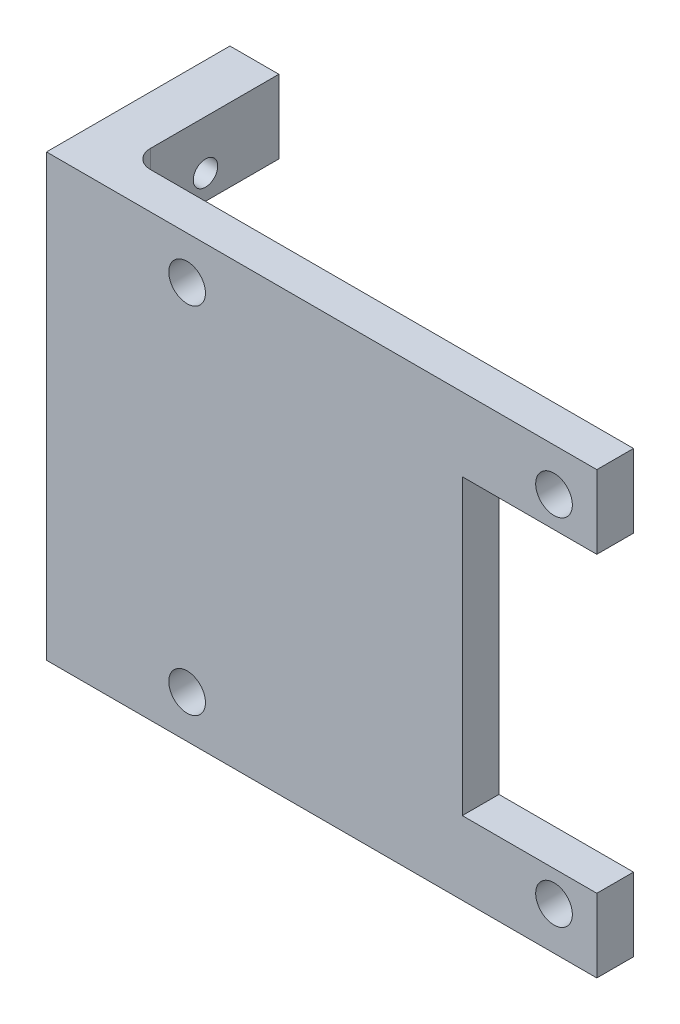
SolidWorks part; units mm, degrees
ref_plane "Front Plane" through (0, 0, 0) normal (0, 0, 1) x (1, 0, 0)
ref_plane "Top Plane" through (0, 0, 0) normal (0, 1, 0) x (1, 0, 0)
ref_plane "Right Plane" through (0, 0, 0) normal (1, 0, 0) x (0, 0, -1)
sketch "Sketch1" plane through (0, 0, 0) normal (0, 0, 1) x (1, 0, 0)
  line L1 (-18.5, 18) -> (18.5, 18)
  line L2 (-18.5, 18) -> (-18.5, -18)
  line L3 (-18.5, -18) -> (18.5, -18)
  line L4 (18.5, 18) -> (18.5, 12)
  line L8 (18.5, 12) -> (7.5, 12)
  line L9 (7.5, 12) -> (7.5, -12)
  line L10 (7.5, -12) -> (18.5, -12)
  line L11 (18.5, -12) -> (18.5, -18)
  point P0 (0, 0)
  dimension "D1" = 36
  dimension "D2" = 37
  dimension "D3" = 18.5
  dimension "D4" = 18
  dimension "D5" = 24
  dimension "D6" = 12
  dimension "D7" = 11
extrude "Boss-Extrude1" add sketch "Sketch1" along normal blind 3
sketch "Sketch2" plane through (0, 0, 0) normal (0, 0, 1) x (1, 0, 0)
  line L0 (-18.5, -18) -> (18.5, -18) construction
  line L1 (-18.5, 18) -> (-18.5, -18) construction
  line L4 (0, -8.25) -> (0, 8.25) construction
  line L5 (8.25, 0) -> (-8.25, 0) construction
  circle A0 centre (-15, -14.5) radius 1.5
  circle A4 centre (15, -14.5) radius 1.5
  circle A5 centre (15, 14.5) radius 1.5
  circle A6 centre (-15, 14.5) radius 1.5
  dimension "D1" = 3
  dimension "D2" = 3.5
  dimension "D3" = 3.5
extrude "Cut-Extrude1" cut sketch "Sketch2" along normal up to next
ref_plane "Plane2" through (-18.5, 0, 0) normal (-1, 0, 0) x (0, 0, 1)
sketch "Sketch6" plane through (-18.5, 0, 0) normal (-1, 0, 0) x (0, 0, 1)
  line L4 (0, 18) -> (0, -18)
  line L5 (0, -18) -> (3, -18)
  line L6 (3, -18) -> (3, 18)
  line L7 (3, 18) -> (0, 18)
  line L8 (0, 18) -> (0, -18)
  line L9 (0, -18) -> (3, -18)
  line L10 (3, -18) -> (3, 18)
  line L11 (3, 18) -> (0, 18)
  dimension "D1" = 0
extrude "Boss-Extrude3" add sketch "Sketch6" along normal blind 8
sketch "Sketch9" plane through (0, 0, 0) normal (0, 0, 1) x (1, 0, 0)
  line L0 (-22.5, 18) -> (-22.5, 12)
  line L1 (18.5, 18) -> (-26.5, 18) construction
  line L2 (-22.5, 12) -> (-26.5, 12)
  line L3 (-26.5, 18) -> (-26.5, -18) construction
  line L4 (-26.5, 12) -> (-26.5, 18)
  line L5 (-26.5, 18) -> (-22.5, 18)
  line L6 (8.25, 0) -> (-8.25, 0) construction
  line L7 (-26.5, -12) -> (-26.5, -18)
  line L8 (-22.5, -12) -> (-26.5, -12)
  line L9 (-22.5, -18) -> (-22.5, -12)
  line L10 (-26.5, -18) -> (-22.5, -18)
  dimension "D1" = 24
  dimension "D2" = 4
extrude "Boss-Extrude4" add sketch "Sketch9" against normal blind 12
ref_plane "Plane3" through (-22.5, 0, 0) normal (1, 0, 0) x (0, 0, -1)
sketch "Sketch10" plane through (-22.5, 0, 0) normal (1, 0, 0) x (0, 0, -1)
  line L0 (12, 18) -> (0, 18) construction
  line L1 (12, 12) -> (12, 18) construction
  line L3 (8.25, 0) -> (-8.25, 0) construction
  circle A0 centre (6, 14) radius 1
  circle A1 centre (6, -14) radius 1
  dimension "D2" = 2
  dimension "D1" = 4
  dimension "D3" = 6
extrude "Cut-Extrude2" cut sketch "Sketch10" against normal up to next
fillet "Fillet1" radius 1.5 4 edges at (-24.5, 12, 0) (-22.5, 15, 0) (-22.5, -15, 0) (-24.5, -12, 0)
